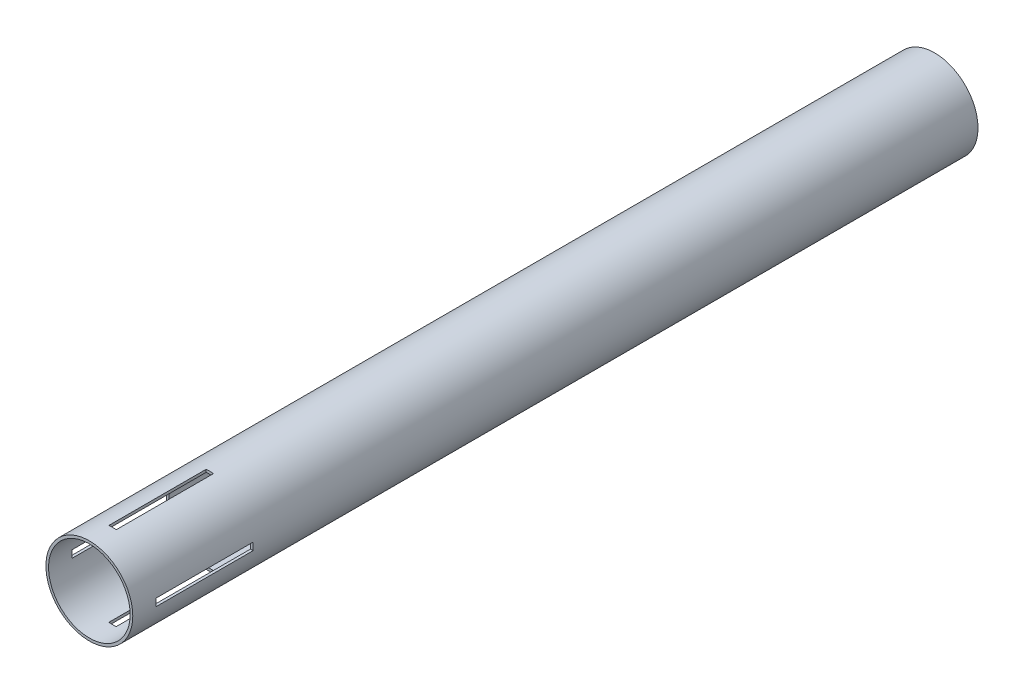
SolidWorks part; units mm, degrees
ref_plane "Front Plane" through (0, 0, 0) normal (0, 0, 1) x (1, 0, 0)
ref_plane "Top Plane" through (0, 0, 0) normal (0, 1, 0) x (1, 0, 0)
ref_plane "Right Plane" through (0, 0, 0) normal (1, 0, 0) x (0, 0, -1)
sketch "Sketch1" plane through (0, 0, 0) normal (0, 0, 1) x (1, 0, 0)
  circle A0 centre (0, 0) radius 20.555
  circle A1 centre (0, 0) radius 19.305
  dimension "D1" = 41.11
  dimension "D2" = 38.61
extrude "Boss-Extrude3" add sketch "Sketch1" against normal blind 400
sketch "Sketch2" plane through (0, 0, 0) normal (0, 1, 0) x (1, 0, 0)
  line L0 (0, -22.6105) -> (0, 22.6105) construction
  line L1 (-1.75, 57) -> (1.75, 57)
  line L2 (-1.75, 57) -> (-1.75, 11)
  line L3 (-1.75, 11) -> (1.75, 11)
  line L4 (1.75, 57) -> (1.75, 11)
  line L5 (-1.75, 57) -> (1.75, 11) construction
  line L6 (-1.75, 11) -> (1.75, 57) construction
  line L7 (-22.6105, 0) -> (22.6105, 0) construction
  point P0 (0, 34)
  dimension "D1" = 3.5
  dimension "D2" = 46
  dimension "D3" = 11
extrude "Cut-Extrude1" cut sketch "Sketch2" against normal through all both and the other way through all
pattern_circular "CirPattern1" count 2 over 90 about axis through (0, 0, -400) along (0, 0, 1) of "Cut-Extrude1" reverse direction yes
